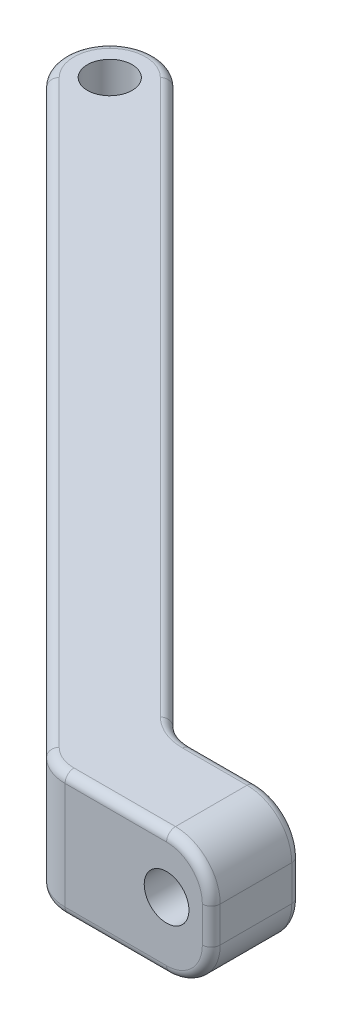
SolidWorks part; units mm, degrees
ref_plane "Front Plane" through (0, 0, 0) normal (0, 0, 1) x (1, 0, 0)
ref_plane "Top Plane" through (0, 0, 0) normal (0, 1, 0) x (1, 0, 0)
ref_plane "Right Plane" through (0, 0, 0) normal (1, 0, 0) x (0, 0, -1)
sketch "Sketch1" plane through (0, 0, 0) normal (0, 1, 0) x (1, 0, 0)
  line L0 (0, 7.0711) -> (-7.0711, 0)
  line L1 (0, 7.0711) -> (66.9211, -59.85)
  line L2 (-7.0711, 0) -> (62.7789, -69.85)
  line L4 (66.9211, -59.85) -> (81.2, -59.85)
  line L5 (81.2, -59.85) -> (81.2, -69.85)
  line L6 (81.2, -69.85) -> (62.7789, -69.85)
  circle A0 centre (0, 0) radius 2.5
  point P6 (76.2, -63.5)
  dimension "D1" = 5
  dimension "D2" = 5
  dimension "D3" = 5
  dimension "D4" = 10
  dimension "D5" = 69.85
  dimension "D6" = 45
  dimension "D7" = 10
  dimension "D8" = 5
  dimension "D9" = 76.2
  dimension "D10" = 63.5
extrude "Boss-Extrude1" add sketch "Sketch1" along normal blind 13.97
sketch "Sketch2" plane through (0, 0, 59.85) normal (0, 0, -1) x (-1, 0, 0)
  line L0 (-81.2, 13.97) -> (-81.2, 0) construction
  line L2 (-81.2, 13.97) -> (-66.9211, 13.97) construction
  circle A0 centre (-76.2, 7.62) radius 2.5
  dimension "D1" = 5
  dimension "D2" = 5
  dimension "D3" = 6.35
extrude "Cut-Extrude1" cut sketch "Sketch2" against normal up to next
sketch "Sketch3" plane through (0, 0, 59.85) normal (0, 0, -1) x (-1, 0, 0)
  line L0 (-78.3389, 11.995) -> (-84.7617, 11.995)
  line L1 (-71.1482, 7.62) -> (-73.6741, 11.995)
  line L2 (-73.6741, 11.995) -> (-78.7259, 11.995)
  line L3 (-78.7259, 11.995) -> (-81.2518, 7.62)
  line L4 (-81.2518, 7.62) -> (-78.7259, 3.245)
  line L5 (-78.7259, 3.245) -> (-73.6741, 3.245)
  line L6 (-73.6741, 3.245) -> (-71.1482, 7.62)
  line L7 (-84.7617, 11.995) -> (-84.7617, 3.245)
  line L8 (-78.7259, 3.245) -> (-84.7617, 3.245)
  circle A0 centre (-76.2, 7.62) radius 4.375 construction
  dimension "D1" = 8.75
fillet "Fillet1" radius 5 6 edges at (0, 6.985, -7.0711) (-7.0711, 6.985, 0) (81.2, 0, 64.85) (81.2, 13.97, 64.85) (62.7789, 6.985, 69.85) (66.9211, 6.985, 59.85)
fillet "Fillet2" radius 1 22 edges at (-5, 0, 0) (0, 0, -5) (34.4961, 0, 27.425) (67.0787, 0, 59.4694) (72.5961, 0, 59.85) (79.7355, 1.4645, 59.85) (81.2, 6.985, 59.85) (79.7355, 12.5055, 59.85) (72.5961, 13.97, 59.85) (67.0787, 13.97, 59.4694) (34.4961, 13.97, 27.425) (0, 13.97, -5) (-5, 13.97, 0) (28.8895, 13.97, 35.9605) (62.9366, 13.97, 69.4694) (70.525, 13.97, 69.85) (79.7355, 12.5055, 69.85) (81.2, 6.985, 69.85) (79.7355, 1.4645, 69.85) (70.525, 0, 69.85) (62.9366, 0, 69.4694) (28.8895, 0, 35.9605)
